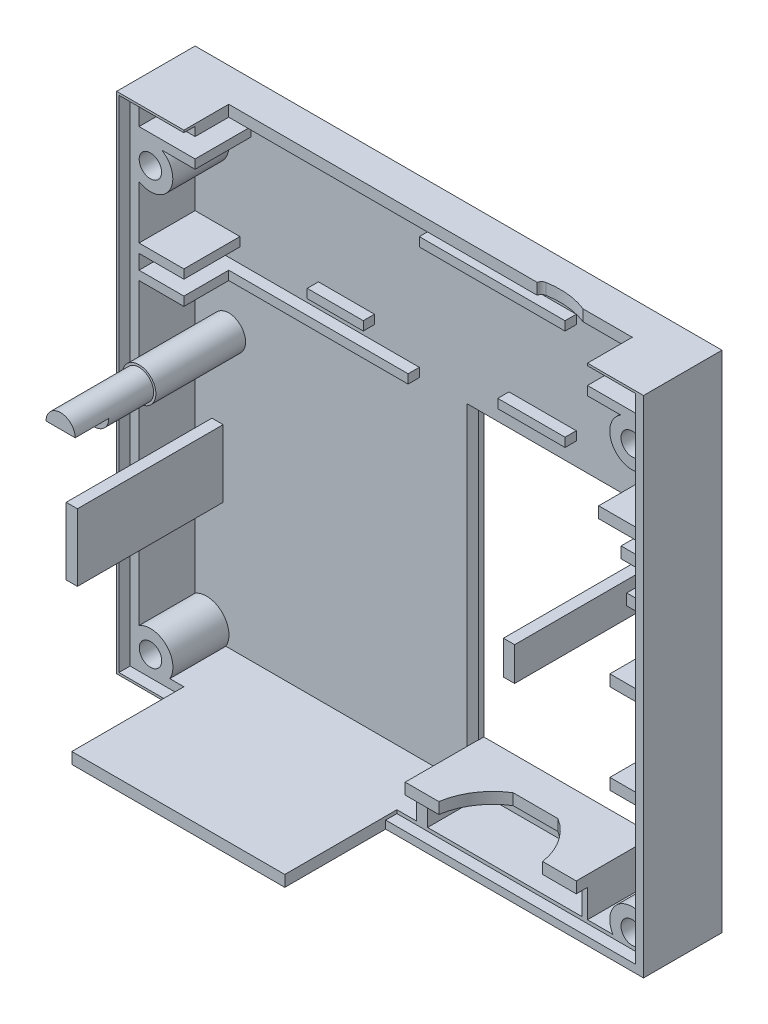
SolidWorks part; units mm, degrees
ref_plane "Piano frontale" through (0, 0, 0) normal (0, 0, 1) x (1, 0, 0)
ref_plane "Piano superiore" through (0, 0, 0) normal (0, 1, 0) x (1, 0, 0)
ref_plane "Piano destro" through (0, 0, 0) normal (1, 0, 0) x (0, 0, -1)
sketch "Schizzo1" plane through (0, 0, 0) normal (0, 0, 1) x (1, 0, 0)
  line L1 (-23.5, -22.5) -> (23.5, -22.5)
  line L2 (-23.5, -22.5) -> (-23.5, 22.5)
  line L3 (-23.5, 22.5) -> (23.5, 22.5)
  line L4 (23.5, -22.5) -> (23.5, 22.5)
  line L5 (-23.5, -22.5) -> (23.5, 22.5) construction
  line L6 (-23.5, 22.5) -> (23.5, -22.5) construction
  point P0 (0, 0)
  dimension "D1" = 47
  dimension "D2" = 45
extrude "Estrusione-Estrusione1" add sketch "Schizzo1" along normal blind 16
sketch "Schizzo3" plane through (0, -22.5, 0) normal (0, -1, 0) x (1, 0, 0)
  line L1 (-23.5, 16) -> (-18.5, 16)
  line L2 (-23.5, 16) -> (-23.5, 7)
  line L3 (-23.5, 7) -> (-18.5, 7)
  line L4 (-18.5, 16) -> (-18.5, 7)
  line L5 (23.5, 16) -> (0.5, 16)
  line L6 (23.5, 16) -> (23.5, 7)
  line L7 (23.5, 7) -> (0.5, 7)
  line L8 (0.5, 16) -> (0.5, 7)
  dimension "D1" = 23
  dimension "D2" = 9
  dimension "D3" = 9
  dimension "D4" = 5
extrude "Taglio-Estrusione1" cut sketch "Schizzo3" against normal through all
sketch "Schizzo4" plane through (-18.5, 0, 0) normal (-1, 0, 0) x (0, 0, 1)
  line L0 (16, 22.5) -> (16, -22.5) construction
  line L1 (16, -21.5) -> (7, -21.5)
  line L2 (16, -21.5) -> (16, 22.5)
  line L3 (16, 22.5) -> (7, 22.5)
  line L12 (7, -21.5) -> (7, 22.5)
  line L13 (7, -22.5) -> (16, -22.5) construction
  dimension "D1" = 1
extrude "Taglio-Estrusione2" cut sketch "Schizzo4" against normal up to next
sketch "Schizzo5" plane through (0, 0, 7) normal (0, 0, 1) x (1, 0, 0)
  line L8 (-18.5, -21.5) -> (-18.5, -22.3)
  line L9 (-18.5, -21.5) -> (-18.5, -22.5) construction
  line L10 (-18.5, -22.3) -> (-23.3, -22.3)
  line L11 (-23.3, -22.3) -> (-23.3, 22.3)
  line L12 (-23.3, 22.3) -> (22.8, 22.3)
  line L13 (22.8, 22.3) -> (22.8, -21.8)
  line L14 (22.8, -21.8) -> (0.5, -21.8)
  line L15 (0.5, -21.8) -> (0.5, -21.5)
  line L16 (0.5, -21.5) -> (-18.5, -21.5)
  line L17 (0.5, -22.5) -> (23.5, -22.5) construction
  line L18 (23.5, 22.5) -> (23.5, -22.5) construction
  line L19 (-23.5, 22.5) -> (23.5, 22.5) construction
  line L20 (-23.5, 22.5) -> (-23.5, -22.5) construction
  line L21 (-23.5, -22.5) -> (-18.5, -22.5) construction
  line L22 (0.5, -21.5) -> (0.5, -22.5) construction
  point P21 (-20.9, -22.3)
  dimension "D1" = 0.7
  dimension "D2" = 0.7
  dimension "D3" = 0.2
  dimension "D4" = 0.2
  dimension "D5" = 0.2
extrude "Taglio-Estrusione3" cut sketch "Schizzo5" against normal blind 1
hole_wizard "Foro per Vite M3-1" positions "Schizzo9" profile "Schizzo10" hole size "M3" standard "Ansi Metric"
sketch "Schizzo9" plane through (0, 0, 6) normal (0, 0, 1) x (1, 0, 0)
  line L2 (-23.3, 22.3) -> (-23.3, -22.3) construction
  line L3 (-23.3, -22.3) -> (-18.5, -22.3) construction
  line L4 (0.5, -22.5) -> (23.5, -22.5) construction
  line L5 (23.5, 22.5) -> (23.5, -22.5) construction
  line L6 (-23.5, 22.5) -> (23.5, 22.5) construction
  line L8 (-23.5, 22.5) -> (-23.5, -22.5) construction
  point P0 (-21.49, 17.25)
  point P3 (-21.48, -20.49)
  point P6 (21.49, -20.49)
  point P9 (21.49, 17.25)
  dimension "D1" = 2.01
  dimension "D2" = 5.25
  dimension "D3" = 1.82
  dimension "D4" = 1.81
  dimension "D5" = 2.01
  dimension "D6" = 2.01
  dimension "D7" = 2.01
  dimension "D8" = 5.25
sketch "Schizzo10" plane through (-21.49, 17.25, 6) normal (1, 0, 0) x (0, -1, 0)
  line L0 (0, 0) -> (0, 4)
  line L1 (0, 4) -> (1, 4)
  line L2 (1, 4) -> (1, 0)
  line L5 (1, 0) -> (0, 0)
  line L10 (0, 4) -> (-1, 4) construction
  line L11 (0, -6.35) -> (0, 107.95) construction
  dimension "Hole Dia." = 2
  dimension "Hole Depth" = 4
  dimension "Drill Angle" = 180
shell "Svuota1" thickness 1 removed face at (-20.49, 17.25, 6)
sketch "Schizzo11" plane through (0, 0, 1) normal (0, 0, 1) x (1, 0, 0)
  line L0 (0.5, -22.5) -> (23.5, -22.5) construction
  line L1 (2.26, -18) -> (17.26, -18)
  line L2 (2.26, -18) -> (2.26, 8)
  line L3 (2.26, 8) -> (17.26, 8)
  line L4 (17.26, -18) -> (17.26, 8)
  line L5 (2.26, -18) -> (17.26, 8) construction
  line L6 (2.26, 8) -> (17.26, -18) construction
  line L7 (23.5, -22.5) -> (23.5, 22.5) construction
  point P0 (9.76, -5)
  dimension "D1" = 15
  dimension "D2" = 26
  dimension "D3" = 4.5
  dimension "D4" = 6.24
extrude "Taglio-Estrusione4" cut sketch "Schizzo11" against normal through all
sketch "Schizzo12" plane through (0, 22.5, 0) normal (0, 1, 0) x (1, 0, 0)
  line L0 (-23.5, -7) -> (23.5, -7) construction
  line L1 (-17.5, -7) -> (18.5, -7)
  line L2 (-17.5, -7) -> (-17.5, -3)
  line L3 (-17.5, -3) -> (18.5, -3)
  line L4 (18.5, -7) -> (18.5, -3)
  line L5 (-23.5, -7) -> (-23.5, 0) construction
  line L6 (23.5, -7) -> (23.5, 0) construction
  line L7 (23.5, 0) -> (-23.5, 0) construction
  dimension "D1" = 6
  dimension "D2" = 5
  dimension "D3" = 3
extrude "Taglio-Estrusione5" cut sketch "Schizzo12" against normal up to surface (1 mm away) and the other way through all up to face at (0, 21.5, 3.5)
sketch "Schizzo13" plane through (0, 0, 1) normal (0, 0, 1) x (1, 0, 0)
  line L0 (17.5, -21.5) -> (17.5, -18)
  line L1 (-19.7538, -21.5) -> (19.7638, -21.5) construction
  line L2 (17.5, -18) -> (2.24, -18)
  line L3 (2.24, -18) -> (2.24, -21.5)
  line L4 (2.24, -21.5) -> (3.24, -21.5)
  line L5 (3.24, -21.5) -> (3.24, -19)
  line L6 (3.24, -19) -> (17, -19)
  line L7 (17, -19) -> (17, -21.5)
  line L8 (17, -21.5) -> (17.5, -21.5)
  line L9 (2.26, -18) -> (17.26, -18) construction
  line L10 (23.5, 22.5) -> (23.5, -22.5) construction
  dimension "D1" = 1
  dimension "D2" = 1
  dimension "D3" = 0.5
  dimension "D4" = 6
  dimension "D5" = 15.26
extrude "Estrusione-Estrusione2" add sketch "Schizzo13" along normal blind 6
sketch "Schizzo14" plane through (2.24, 0, 0) normal (-1, 0, 0) x (0, 0, 1)
  line L10 (7, -18) -> (7, -21.5) construction
  line L11 (6, -21.5) -> (7, -21.5)
  line L12 (6, -21.5) -> (6, -19)
  line L13 (6, -19) -> (7, -19)
  line L14 (7, -21.5) -> (7, -19)
  line L15 (7, -18) -> (1, -18) construction
  line L16 (6, -21.5) -> (16, -21.5) construction
  dimension "D1" = 1
  dimension "D2" = 1
extrude "Taglio-Estrusione6" cut sketch "Schizzo14" against normal up to surface (15.26 mm away) up to face at (17.5, -20.1, 4.4)
sketch "Schizzo15" plane through (0, -18, 0) normal (0, 1, 0) x (1, 0, 0)
  line L0 (17.5, -7) -> (2.24, -7) construction
  line L1 (7.87, -3) -> (11.87, -3)
  line L2 (2.26, 0) -> (17.26, 0) construction
  line L3 (2.24, -7) -> (2.24, -1) construction
  line L4 (17.5, -7) -> (17.5, -1) construction
  line L5 (9.87, -3) -> (9.87, -7) construction
  line L6 (5.24, -7) -> (14.5, -7)
  arc A0 (14.5, -7) -> (11.87, -3) centre (8.8153, -7.8731) ccw
  arc A1 (5.24, -7) -> (7.87, -3) centre (10.9247, -7.8731) cw
  point P0 (4.51, -7)
  point P1 (14.5, -7)
  point P7 (9.87, -3)
  point P15 (9.87, -7)
  point P20 (0, 0)
  point P21 (0, 0)
  dimension "D5" = 5.7514
  dimension "D1" = 3
  dimension "D2" = 2.27
  dimension "D3" = 3
  dimension "D4" = 4
extrude "Taglio-Estrusione7" cut sketch "Schizzo15" against normal up to next
chamfer "Smusso1" distance 0.5 angle 45 2 edges at (2.26, -5, 1) (17.26, -5, 1)
sketch "Schizzo16" plane through (0, 0, 1) normal (0, 0, 1) x (1, 0, 0)
  line L0 (22.5, -9.5) -> (22.5, -10.5)
  line L1 (22.5, -18.7638) -> (22.5, 15.5238) construction
  line L2 (22.5, -10.5) -> (19.5, -10.5)
  line L3 (19.5, -10.5) -> (19.5, -1.5)
  line L4 (19.5, -1.5) -> (22.5, -1.5)
  line L5 (22.5, -1.5) -> (22.5, -2.5)
  line L6 (22.5, -2.5) -> (20.5, -2.5)
  line L7 (20.5, -2.5) -> (20.5, -9.5)
  line L8 (20.5, -9.5) -> (22.5, -9.5)
  line L10 (22.5, 10.98) -> (18.5, 10.98)
  line L11 (18.5, 10.98) -> (18.5, 9.98)
  line L12 (18.5, 9.98) -> (22.5, 9.98)
  line L13 (22.5, 9.98) -> (22.5, 10.98)
  line L14 (22.5, 8.88) -> (20.5, 8.88)
  line L15 (20.5, 8.88) -> (20.5, 7.88)
  line L16 (20.5, 7.88) -> (22.5, 7.88)
  line L17 (22.5, 15.5238) -> (22.5, -18.7638) construction
  line L18 (22.5, 7.88) -> (22.5, 8.88)
  line L19 (-22.5, 8.68) -> (-2.5, 8.68)
  line L20 (-22.5, 15.5238) -> (-22.5, -18.7697) construction
  line L21 (-2.5, 8.68) -> (-2.5, 7.88)
  line L22 (-2.5, 7.88) -> (-22.5, 7.88)
  line L23 (-22.5, 7.88) -> (-22.5, 8.68)
  line L24 (-18.5, 10.78) -> (-22.5, 10.78)
  line L25 (-22.5, 10.78) -> (-22.5, 9.98)
  line L26 (-22.5, 9.98) -> (-18.5, 9.98)
  line L27 (-18.5, 9.98) -> (-18.5, 10.78)
  line L28 (-22.5, 19.7762) -> (-17.5, 19.7762)
  line L29 (-22.5, 21.5) -> (-22.5, 18.9762) construction
  line L30 (-17.5, 19.7762) -> (-17.5, 18.9762)
  line L31 (-17.5, 18.9762) -> (-22.5, 18.9762)
  line L32 (-22.5, 18.9762) -> (-22.5, 19.7762)
  line L33 (22.5, 18.9762) -> (17.5, 18.9762)
  line L34 (17.5, 18.9762) -> (17.5, 19.7762)
  line L35 (17.5, 19.7762) -> (22.5, 19.7762)
  line L36 (22.5, 18.9762) -> (22.5, 21.5) construction
  line L37 (22.5, 19.7762) -> (22.5, 18.9762)
  line L38 (0.5, -22.5) -> (23.5, -22.5) construction
  line L39 (11.5, 19.7762) -> (-1.5, 19.7762)
  line L40 (11.5, 19.7762) -> (11.5, 18.9762)
  line L41 (11.5, 18.9762) -> (-1.5, 18.9762)
  line L42 (-1.5, 19.7762) -> (-1.5, 18.9762)
  line L51 (11.5, 10.78) -> (5.5, 10.78)
  line L52 (11.5, 10.78) -> (11.5, 9.98)
  line L53 (11.5, 9.98) -> (5.5, 9.98)
  line L54 (5.5, 10.78) -> (5.5, 9.98)
  line L55 (-6.5, 10.78) -> (-11.5, 10.78)
  line L56 (-6.5, 10.78) -> (-6.5, 9.98)
  line L57 (-6.5, 9.98) -> (-11.5, 9.98)
  line L58 (-11.5, 10.78) -> (-11.5, 9.98)
  line L59 (18.5, 22.5) -> (23.5, 22.5) construction
  line L61 (22.5, 5.5) -> (21, 5.5)
  line L62 (22.5, 5.5) -> (22.5, 4.5)
  line L63 (22.5, 4.5) -> (21, 4.5)
  line L64 (21, 5.5) -> (21, 4.5)
  dimension "D1" = 1
  dimension "D2" = 1
  dimension "D3" = 1
  dimension "D4" = 3
  dimension "D5" = 12
  dimension "D6" = 9
  dimension "D7" = 1
  dimension "D8" = 1.1
  dimension "D9" = 11.52
  dimension "D10" = 2
  dimension "D11" = 4
  dimension "D12" = 2
  dimension "D13" = 5
  dimension "D14" = 5
  dimension "D15" = 4
  dimension "D16" = 20
  dimension "D17" = 7
  dimension "D18" = 7
  dimension "D19" = 12
  dimension "D20" = 5
  dimension "D21" = 13
  dimension "D22" = 6
  dimension "D23" = 1.5
  dimension "D24" = 1
  dimension "D25" = 6
  dimension "D26" = 0.8
extrude "Estrusione-Estrusione3" add sketch "Schizzo16" along normal up to surface (5 mm away) up to face at (-20.3897, 1.5267, 6)
sketch "Schizzo17" plane through (19.5, 0, 0) normal (-1, 0, 0) x (0, 0, 1)
  line L0 (6, -10.5) -> (6, -1.5) construction
  line L1 (6, -2.5) -> (2, -2.5)
  line L2 (6, -2.5) -> (6, -9.5)
  line L3 (6, -9.5) -> (2, -9.5)
  line L4 (2, -2.5) -> (2, -9.5)
  line L5 (1, -1.5) -> (1, -10.5) construction
  line L6 (6, -1.5) -> (1, -1.5) construction
  line L7 (6, -10.5) -> (1, -10.5) construction
  dimension "D1" = 1
  dimension "D2" = 1
  dimension "D3" = 1
extrude "Taglio-Estrusione8" cut sketch "Schizzo17" against normal up to next
sketch "Schizzo18" plane through (0, 19.7762, 0) normal (0, 1, 0) x (1, 0, 0)
  line L1 (11.5, -2) -> (-17.5, -2)
  line L2 (11.5, -2) -> (11.5, -6)
  line L3 (11.5, -6) -> (-17.5, -6)
  line L4 (-17.5, -2) -> (-17.5, -6)
  line L5 (-1.5, -6) -> (11.5, -6) construction
  line L6 (11.5, -1) -> (-1.5, -1) construction
  line L9 (11.5, -6) -> (11.5, -1) construction
  line L11 (-17.5, -6) -> (-17.5, -1) construction
  dimension "D1" = 1
extrude "Taglio-Estrusione9" cut sketch "Schizzo18" against normal up to surface (11.8962 mm away) up to face at (-12.5, 7.88, 3.5)
sketch "Schizzo19" plane through (0, 8.68, 0) normal (0, 1, 0) x (1, 0, 0)
  line L0 (-22.5, -6) -> (-17.5, -6) construction
  line L1 (-17.5, -2) -> (-18.5, -2)
  line L2 (-17.5, -2) -> (-17.5, -6)
  line L3 (-17.5, -6) -> (-18.5, -6)
  line L4 (-18.5, -2) -> (-18.5, -6)
  line L5 (-18.5, -6) -> (-18.5, -1) construction
extrude "Taglio-Estrusione10" cut sketch "Schizzo19" against normal up to next
sketch "Schizzo20" plane through (0, 0, 1) normal (0, 0, 1) x (1, 0, 0)
  line L0 (21, 4.5) -> (21, 5.5) construction
  line L1 (21, 6.5) -> (20, 6.5)
  line L2 (21, 6.5) -> (21, 3.5)
  line L3 (21, 3.5) -> (20, 3.5)
  line L4 (20, 6.5) -> (20, 3.5)
  line L5 (22.5, 5.5) -> (21, 5.5) construction
  line L6 (21, 4.5) -> (22.5, 4.5) construction
  line L7 (-18.5, 7.88) -> (-22.5, 7.88) construction
  line L8 (-23.5, 22.5) -> (-23.5, -22.5) construction
  circle A0 centre (-19.5, 2.88) radius 1.5
  dimension "D4" = 3
  dimension "D1" = 1
  dimension "D2" = 1
  dimension "D3" = 1
  dimension "D5" = 5
  dimension "D6" = 4
extrude "Estrusione-Estrusione4" add sketch "Schizzo20" along normal blind 15
sketch "Schizzo21" plane through (0, 0, 16) normal (0, 0, 1) x (1, 0, 0)
  circle A0 centre (-19.5, 2.88) radius 1.3
  circle A3 centre (-19.5, 2.88) radius 1.5
  circle A4 centre (-19.5, 2.88) radius 1.5
  dimension "D2" = 0.2
  dimension "D1" = 0
extrude "Taglio-Estrusione11" cut sketch "Schizzo21" against normal blind 7
sketch "Schizzo22" plane through (0, 0, 16) normal (0, 0, 1) x (1, 0, 0)
  line L0 (-20.8, 2.88) -> (-18.2, 2.88)
  circle A1 centre (-19.5, 2.88) radius 1.3
  arc A2 (-20.8, 2.88) -> (-18.2, 2.88) centre (-19.5, 2.88) ccw
  dimension "D1" = 0
extrude "Taglio-Estrusione12" cut sketch "Schizzo22" against normal blind 3
sketch "Schizzo23" plane through (0, 0, 1) normal (0, 0, 1) x (1, 0, 0)
  line L0 (-22.5, 7.88) -> (-22.5, -18.7697) construction
  line L1 (-21, -4.5) -> (-20, -4.5)
  line L2 (-21, -4.5) -> (-21, -10.5)
  line L3 (-21, -10.5) -> (-20, -10.5)
  line L4 (-20, -4.5) -> (-20, -10.5)
  line L5 (-23.5, -22.5) -> (-18.5, -22.5) construction
  dimension "D1" = 1
  dimension "D2" = 1.5
  dimension "D3" = 6
  dimension "D4" = 12
extrude "Estrusione-Estrusione5" add sketch "Schizzo23" along normal blind 13
sketch "Schizzo25" plane through (0, 22.5, 0) normal (0, 1, 0) x (1, 0, 0)
  line L2 (14.1108, -3) -> (10.0116, -3)
  line L3 (-17.5, -3) -> (18.5, -3) construction
  line L4 (23.5, -7) -> (23.5, 0) construction
  arc A1 (14.1108, -3) -> (10.4143, -2.6146) centre (11.5824, -9.3314) ccw
  arc A3 (10.4143, -2.6146) -> (10.0116, -3) centre (10.5, -3.1072) ccw
  dimension "D2" = 0.5
  dimension "D5" = 6.8176
  dimension "D1" = 4.0992
  dimension "D3" = 0.3854
  dimension "D4" = 0.4027
  dimension "D6" = 9.3892
extrude "Taglio-Estrusione14" cut sketch "Schizzo25" against normal up to next
